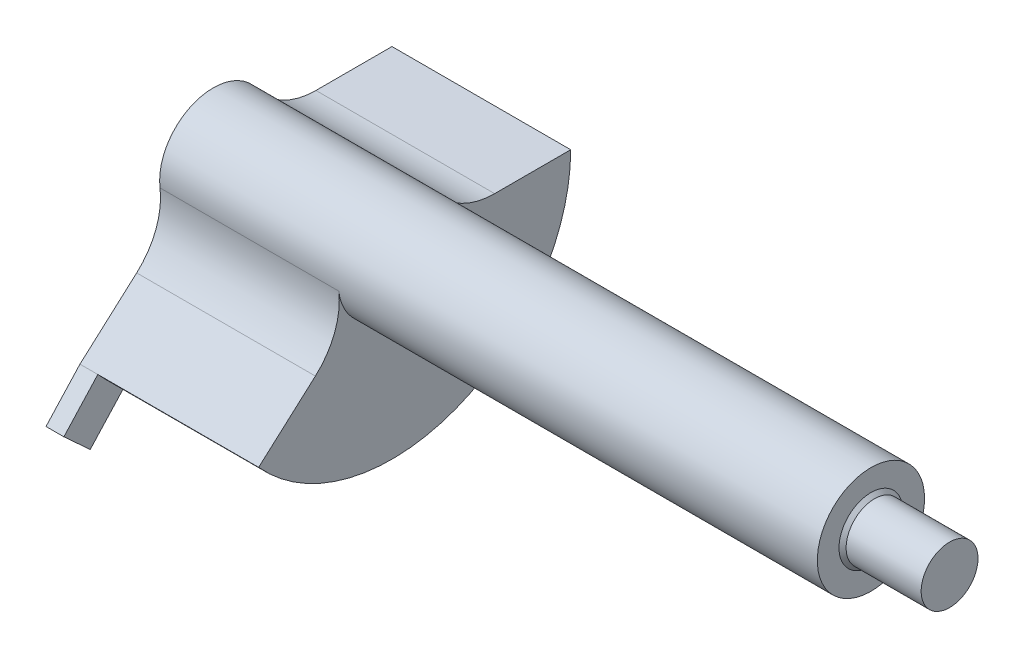
SolidWorks part; units mm, degrees
ref_plane "Front Plane" through (0, 0, 0) normal (0, 0, 1) x (1, 0, 0)
ref_plane "Top Plane" through (0, 0, 0) normal (0, 1, 0) x (1, 0, 0)
ref_plane "Right Plane" through (0, 0, 0) normal (1, 0, 0) x (0, 0, -1)
sketch "Sketch1" plane through (0, 0, 0) normal (1, 0, 0) x (0, 0, -1)
  line L0 (0, 0) -> (-20.425, 0) construction
  line L1 (0, 0) -> (-14.4427, 14.4427) construction
  line L2 (0, 0) -> (14.4427, -14.4427) construction
  line L3 (0, 0) -> (20.425, 0) construction
  line L4 (7.018, -21.8673) -> (8.6183, -23.4675)
  line L5 (21.8673, -7.018) -> (23.4675, -8.6183)
  line L6 (20.425, 10.5) -> (22.6881, 10.5)
  line L7 (20.425, -10.5) -> (22.6881, -10.5)
  line L8 (7.018, 21.8673) -> (8.6183, 23.4675)
  line L9 (21.8673, 7.018) -> (23.4675, 8.6183)
  line L10 (-10.5, 20.425) -> (-10.5, 22.6881)
  line L11 (10.5, 20.425) -> (10.5, 22.6881)
  line L12 (-21.8673, 7.018) -> (-23.4675, 8.6183)
  line L13 (-7.018, 21.8673) -> (-8.6183, 23.4675)
  line L14 (-20.425, -10.5) -> (-22.6881, -10.5)
  line L15 (-20.425, 10.5) -> (-22.6881, 10.5)
  line L16 (0, 0) -> (7.018, -21.8673) construction
  line L17 (0, 0) -> (20.425, -10.5) construction
  circle A0 centre (0, 0) radius 25
  circle A1 centre (0, 0) radius 20.425 construction
  circle A2 centre (-20.425, 0) radius 10.5
  circle A3 centre (-20.425, 0) radius 2.575
  circle A4 centre (-14.4427, 14.4427) radius 10.5
  circle A5 centre (-14.4427, 14.4427) radius 2.575
  circle A6 centre (0, 20.425) radius 10.5
  circle A7 centre (0, 20.425) radius 2.575
  circle A8 centre (14.4427, 14.4427) radius 10.5
  circle A9 centre (14.4427, 14.4427) radius 2.575
  circle A10 centre (20.425, 0) radius 10.5
  circle A11 centre (20.425, 0) radius 2.575
  circle A12 centre (14.4427, -14.4427) radius 10.5
  circle A13 centre (14.4427, -14.4427) radius 2.575
  circle A14 centre (14.4427, -14.4427) radius 7
  circle A15 centre (20.425, 0) radius 7
  circle A16 centre (14.4427, 14.4427) radius 7
  circle A17 centre (0, 20.425) radius 7
  circle A18 centre (-14.4427, 14.4427) radius 7
  circle A19 centre (-20.425, 0) radius 7
  dimension "D1" = 6
  dimension "D2" = 5.15
  dimension "D3" = 21
  dimension "D4" = 2
  dimension "D6" = 50
  dimension "D7" = 14
  dimension "D9" = 6
  dimension "D5" = 45
  dimension "D10" = 45
  dimension "D8" = 6
extrude "Boss-Extrude1" add sketch "Sketch1" along normal blind 92 contours A0
sketch "Sketch2" plane through (0, 0, 0) normal (-1, 0, 0) x (0, 0, 1)
  circle A0 centre (0, 0) radius 2.6
  circle A1 centre (0, 0) radius 7.5
  dimension "D1" = 5.2
  dimension "D2" = 15
sketch "Sketch4" plane through (92, 0, 0) normal (1, 0, 0) x (0, 0, -1)
  circle A0 centre (0, 0) radius 3.975
  dimension "D1" = 7.95
extrude "Cut-Extrude1" cut sketch "Sketch1<3>" along normal blind 7 from offset 12 contours A12 A0 L5 L7 | A12 L4 A0 | A12 region at (0, -23.0439, -8.3101) region at (0, -8.3101, -23.0439)
sketch "Sketch1<3>" plane through (0, 0, 0) normal (1, 0, 0) x (0, 0, -1) same geometry as "Sketch1"
extrude "Cut-Extrude2" cut sketch "Sketch1<8>" along normal blind 7 from offset 48 contours A10 L5 L7 A0 | A10 A0 L6 L9 | A10 region at (0, -10.4184, -22.1706) region at (0, 10.4184, -22.1706)
sketch "Sketch1<8>" plane through (0, 0, 0) normal (1, 0, 0) x (0, 0, -1) same geometry as "Sketch1"
extrude "Cut-Extrude3" cut sketch "Sketch1<9>" along normal blind 7 from offset 24 contours A8 L6 L9 A0 | A8 A0 L8 L11 | A8 region at (0, 8.3101, -23.0439) region at (0, 23.0439, -8.3101)
sketch "Sketch1<9>" plane through (0, 0, 0) normal (1, 0, 0) x (0, 0, -1) same geometry as "Sketch1"
extrude "Cut-Extrude7" cut sketch "Sketch1<10>" along normal blind 7 from offset 60 contours A6 L8 L11 A0 | A6 A0 L10 L13 | A6 region at (0, 22.1706, 10.4184) region at (0, 22.1706, -10.4184)
sketch "Sketch1<10>" plane through (0, 0, 0) normal (1, 0, 0) x (0, 0, -1) same geometry as "Sketch1"
extrude "Cut-Extrude8" cut sketch "Sketch1<11>" along normal blind 7 from offset 36 contours A4 L10 L13 A0 | A4 A0 L12 L15 | A4 region at (0, 8.3101, 23.0439) region at (0, 23.0439, 8.3101)
sketch "Sketch1<11>" plane through (0, 0, 0) normal (1, 0, 0) x (0, 0, -1) same geometry as "Sketch1"
extrude "Cut-Extrude9" cut sketch "Sketch1<12>" along normal blind 7 from offset 72 contours A2 A0 L14 | A2 L12 L15 A0 | A2 region at (0, -10.4184, 22.1706) region at (0, 10.4184, 22.1706)
sketch "Sketch1<12>" plane through (0, 0, 0) normal (1, 0, 0) x (0, 0, -1) same geometry as "Sketch1"
extrude "Cut-Extrude10" cut sketch "Sketch1<28>" along normal blind 8 and the other way blind 64 from surface contours A13 starting at face at (19, -13.7953, -13.7953)
sketch "Sketch1<28>" plane through (0, 0, 0) normal (1, 0, 0) x (0, 0, -1) same geometry as "Sketch1"
extrude "Cut-Extrude11" cut sketch "Sketch1<29>" along normal blind 8 and the other way blind 73 from surface contours A9 starting at face at (31, 13.7953, -13.7953)
sketch "Sketch1<29>" plane through (0, 0, 0) normal (1, 0, 0) x (0, 0, -1) same geometry as "Sketch1"
extrude "Cut-Extrude12" cut sketch "Sketch1<30>" along normal blind 8 and the other way blind 183 from surface contours A5 starting at face at (43, 13.7953, 13.7953)
sketch "Sketch1<30>" plane through (0, 0, 0) normal (1, 0, 0) x (0, 0, -1) same geometry as "Sketch1"
extrude "Cut-Extrude13" cut sketch "Sketch1<31>" against normal blind 8 and the other way blind 74 from surface contours A11 starting at face at (48, 0, -19.5095)
sketch "Sketch1<31>" plane through (0, 0, 0) normal (1, 0, 0) x (0, 0, -1) same geometry as "Sketch1"
extrude "Cut-Extrude14" cut sketch "Sketch1<32>" against normal blind 8 and the other way blind 87 from surface contours A7 starting at face at (60, 19.5095, 0)
sketch "Sketch1<32>" plane through (0, 0, 0) normal (1, 0, 0) x (0, 0, -1) same geometry as "Sketch1"
extrude "Cut-Extrude15" cut sketch "Sketch1<33>" against normal blind 8 and the other way blind 124 from surface contours A3 starting at face at (72, 0, 19.5095)
sketch "Sketch1<33>" plane through (0, 0, 0) normal (1, 0, 0) x (0, 0, -1) same geometry as "Sketch1"
extrude "Cut-Extrude16" cut sketch "Sketch2" against normal blind 25 contours A0 region at (0, 0, 0)
extrude "Boss-Extrude2" add sketch "Sketch4" along normal blind 11
sketch "Sketch5" plane through (0, 0, 0) normal (0, 1, 0) x (1, 0, 0)
  line L0 (0, 25) -> (0, -25) construction
  line L1 (2, 4.5) -> (11, 4.5)
  line L2 (2, 4.5) -> (2, -4.5) construction
  line L3 (2, -4.5) -> (11, -4.5)
  line L4 (11, 4.5) -> (11, -4.5)
  line L5 (2, 4.5) -> (11, -4.5) construction
  line L6 (2, -4.5) -> (11, 4.5) construction
  line L7 (2, -4.5) -> (0, -4.5)
  line L8 (0, -4.5) -> (0, 4.5)
  line L9 (0, 4.5) -> (2, 4.5)
  line L10 (0, 3) -> (11, 3)
  line L11 (11, 3) -> (11, -3)
  line L12 (11, -3) -> (0, -3)
  line L13 (0, -3) -> (0, 3)
  line L14 (9.5, 3) -> (9.5, -3)
  circle A0 centre (6.5, 0) radius 1.75
  circle A1 centre (6.5, 0) radius 3.5
  point P0 (6.5, 0)
  dimension "D2" = 3.5
  dimension "D3" = 7
  dimension "D1" = 9
  dimension "D4" = 2
  dimension "D5" = 6
  dimension "D6" = 1.5
  dimension "D7" = 3
extrude "Cut-Extrude17" cut sketch "Sketch5" against normal blind 58 contours A0 region at (6.5, 0, 0)
extrude "Cut-Extrude18" cut sketch "Sketch5<3>" against normal blind 3 from offset 5 contours A1 L14 L10 | L12 A1 L14 L10 A0 | A1 L12 L14 | A1 L10 L8 L12 | A0 region at (1.7807, 0, 0) region at (9.1343, 0, -2.6343) region at (6.5, 0, -2.9115) region at (9.1343, 0, 2.6343) region at (6.5, 0, 0) offset against normal yes
sketch "Sketch5<3>" plane through (0, 0, 0) normal (0, 1, 0) x (1, 0, 0) same geometry as "Sketch5"
extrude "Cut-Extrude19" cut sketch "Sketch5<4>" against normal through all from offset 14 contours A1 offset against normal yes
sketch "Sketch5<4>" plane through (0, 0, 0) normal (0, 1, 0) x (1, 0, 0) same geometry as "Sketch5"
chamfer "Chamfer1" distance 0.5 angle 45 1 edges at (92, 0, -3.975)
sketch "Sketch6" plane through (0, 0, 0) normal (-1, 0, 0) x (0, 0, 1)
  line L0 (0, 0) -> (21.5528, -23.5208) construction
  line L1 (-14.4427, 14.4427) -> (0, 20.425) construction
  line L2 (23.396, -21.8318) -> (19.7096, -25.2097)
  line L3 (0, 0) -> (-7.2213, 17.4338) construction
  line L4 (19.7096, -25.2097) -> (12.9537, -17.837)
  line L5 (12.9537, -17.837) -> (16.6401, -14.459)
  line L6 (16.6401, -14.459) -> (23.396, -21.8318)
  circle A4 centre (0, 0) radius 25 construction
  dimension "D4" = 160
  dimension "D1" = 10
  dimension "D2" = 5
  dimension "D3" = 7
extrude "Boss-Extrude3" add sketch "Sketch6" against normal blind 2.5
sketch "Sketch7" plane through (92, 0, 0) normal (1, 0, 0) x (0, 0, -1)
  line L0 (0, 0) -> (-18.6483, -16.6506)
  line L1 (0, 0) -> (25, 0)
  line L2 (-23.396, -21.8318) -> (-18.6483, -16.6506) construction
  circle A0 centre (0, 0) radius 7.5
  circle A1 centre (0, 0) radius 25
  circle A2 centre (0, 0) radius 25 construction
  circle M2 centre (-20.425, 0) radius 2.575
  circle M3 centre (0, 20.425) radius 2.575
  circle M4 centre (20.425, 0) radius 2.575
  circle M5 centre (0, 0) radius 25
  dimension "D1" = 15
extrude "Cut-Extrude20" cut sketch "Sketch7" against normal blind 67 contours A0 L0 L1 M5 M4 | A0 L1 L0 M4 M5 M2 M3 | M2 | M3 | L1 M4 | L1 M4 region at (92, -13.0774, -4.6803) region at (92, 8.0213, 3.0159) region at (92, 1.0929, -20.425) region at (92, -1.0929, -20.425) region at (92, 0, 20.425) region at (92, 20.425, 0)
extrude "Cut-Extrude22" cut sketch "Sketch7<6>" against normal blind 123 contours A0 L1 L0 M4 M5 M2 M3 | M2 | M3 | L1 M4 region at (92, 8.0213, 3.0159) region at (92, 1.0929, -20.425) region at (92, 0, 20.425) region at (92, 20.425, 0)
sketch "Sketch7<6>" plane through (92, 0, 0) normal (1, 0, 0) x (0, 0, -1) same geometry as "Sketch7"
fillet "Fillet1" radius 10 2 edges at (12.5, 0, -7.5) (12.5, -4.9952, 5.5945)
